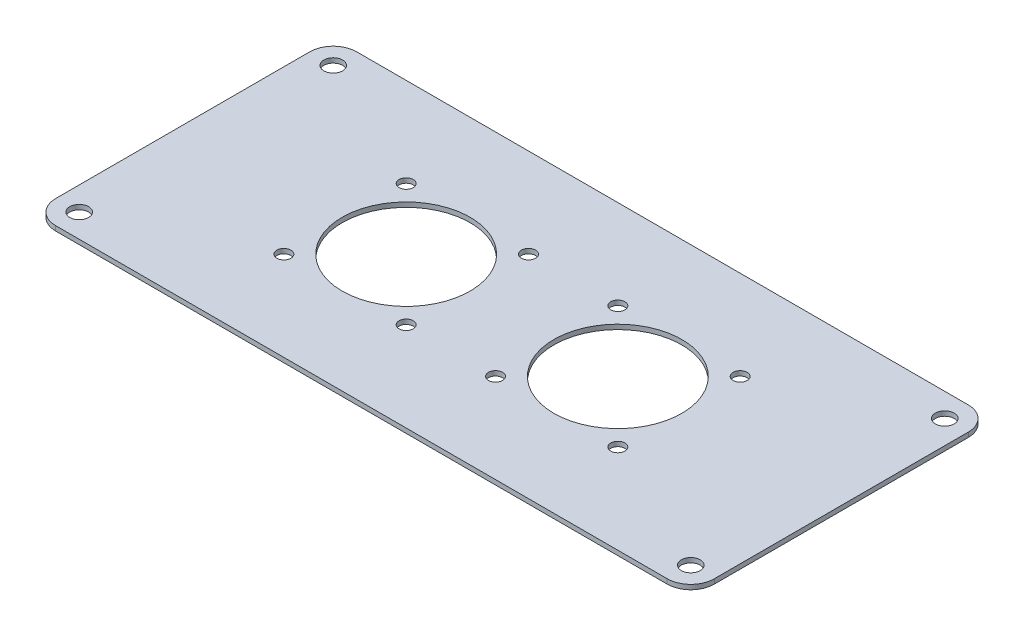
SolidWorks part; units mm, degrees
ref_plane "Спереди" through (0, 0, 0) normal (0, 0, 1) x (1, 0, 0)
ref_plane "Сверху" through (0, 0, 0) normal (0, 1, 0) x (1, 0, 0)
ref_plane "Справа" through (0, 0, 0) normal (1, 0, 0) x (0, 0, -1)
sketch "Эскиз1" plane through (0, 0, 0) normal (0, 1, 0) x (1, 0, 0)
  line L1 (-53.7713, 34.1946) -> (86.2287, 34.1946)
  line L2 (-53.7713, 34.1946) -> (-53.7713, -29.8054)
  line L3 (-53.7713, -29.8054) -> (86.2287, -29.8054)
  line L4 (86.2287, 34.1946) -> (86.2287, -29.8054)
  dimension "D1" = 64
  dimension "D2" = 140
sheet metal parameters "Листовой металл1" thickness 1 parameters "D1"=1.1, "Толщина"=1
base flange "Базовая кромка1" sketch "Эскиз1" thickness 1 reverse thickness direction no parameters "D1"=1.1
fillet "Скругление1" radius 5 4 edges at (86.2287, -0.5, -34.1946) (86.2287, -0.5, 29.8054) (-53.7713, -0.5, -34.1946) (-53.7713, -0.5, 29.8054)
sketch "Эскиз4" plane through (0, 0, 0) normal (0, 1, 0) x (1, 0, 0)
  line L0 (-53.7713, 2.1946) -> (86.2287, 2.1946) construction
  line L1 (-48.7713, -24.8054) -> (81.2287, -24.8054) construction
  line L2 (-48.7713, -24.8054) -> (-48.7713, 29.1946) construction
  line L3 (-48.7713, 29.1946) -> (81.2287, 29.1946) construction
  line L4 (81.2287, -24.8054) -> (81.2287, 29.1946) construction
  line L5 (-53.7713, 29.1946) -> (-53.7713, -24.8054) construction
  line L6 (86.2287, -24.8054) -> (86.2287, 29.1946) construction
  line L7 (86.2287, 2.1946) -> (16.2287, 34.1946) construction
  line L8 (81.2287, 34.1946) -> (-48.7713, 34.1946) construction
  line L9 (16.2287, 34.1946) -> (16.2287, -29.8054) construction
  line L10 (-48.7713, -29.8054) -> (81.2287, -29.8054) construction
  circle A0 centre (-48.7713, 29.1946) radius 2
  circle A1 centre (81.2287, 29.1946) radius 2
  circle A2 centre (-48.7713, -24.8054) radius 2
  circle A3 centre (81.2287, -24.8054) radius 2
  dimension "D5" = 4
  dimension "D6" = 4
  dimension "D7" = 4
  dimension "D8" = 4
  dimension "D1" = 5
  dimension "D2" = 5
  dimension "D3" = 5
  dimension "D4" = 5
extrude "Вырез-Вытянуть2" cut sketch "Эскиз4" against normal blind 10 normal cut yes
sketch "Эскиз5" plane through (0, 0, 0) normal (0, 1, 0) x (1, 0, 0)
  line L0 (-53.7713, 2.1946) -> (86.2287, 2.1946) construction
  line L1 (-53.7713, 29.1946) -> (-53.7713, -24.8054) construction
  line L2 (86.2287, -24.8054) -> (86.2287, 29.1946) construction
  line L3 (16.2287, 34.1946) -> (16.2287, -29.8054) construction
  line L6 (-19.2713, 15.1946) -> (6.7287, 15.1946) construction
  line L11 (-19.2713, 15.1946) -> (-19.2713, -10.8054) construction
  line L13 (-19.2713, -10.8054) -> (6.7287, -10.8054) construction
  line L15 (6.7287, 15.1946) -> (6.7287, -10.8054) construction
  line L16 (25.7287, 15.1946) -> (51.7287, 15.1946) construction
  line L17 (25.7287, 15.1946) -> (25.7287, -10.8054) construction
  line L18 (25.7287, -10.8054) -> (51.7287, -10.8054) construction
  line L21 (51.7287, 15.1946) -> (51.7287, -10.8054) construction
  line L22 (81.2287, 34.1946) -> (-48.7713, 34.1946) construction
  line L23 (-48.7713, -29.8054) -> (81.2287, -29.8054) construction
  circle A0 centre (-6.2713, 2.1946) radius 13.6
  circle A1 centre (38.7287, 2.1946) radius 13.6
  circle A2 centre (-19.2713, 15.1946) radius 1.5
  circle A3 centre (6.7287, 15.1946) radius 1.5
  circle A4 centre (-19.2713, -10.8054) radius 1.5
  circle A5 centre (6.7287, -10.8054) radius 1.5
  circle A6 centre (25.7287, 15.1946) radius 1.5
  circle A7 centre (51.7287, 15.1946) radius 1.5
  circle A8 centre (25.7287, -10.8054) radius 1.5
  circle A9 centre (51.7287, -10.8054) radius 1.5
  dimension "D13" = 3
  dimension "D1" = 27.2
  dimension "D2" = 27.2
  dimension "D3" = 45
  dimension "D9" = 13
  dimension "D11" = 13
  dimension "D12" = 3
  dimension "D14" = 3
  dimension "D15" = 3
  dimension "D16" = 3
  dimension "D17" = 3
  dimension "D18" = 3
  dimension "D19" = 3
  dimension "D20" = 22.5
  dimension "D4" = 26
  dimension "D5" = 26
  dimension "D6" = 26
  dimension "D7" = 26
  dimension "D8" = 13
  dimension "D10" = 13
extrude "Вырез-Вытянуть3" cut sketch "Эскиз5" against normal blind 10 normal cut yes
flat pattern "Развертка1" [suppressed]
sketch "Сгиб-Линии1" plane through (0, 0, 0) normal (0, 1, 0) x (-1, 0, 0)
